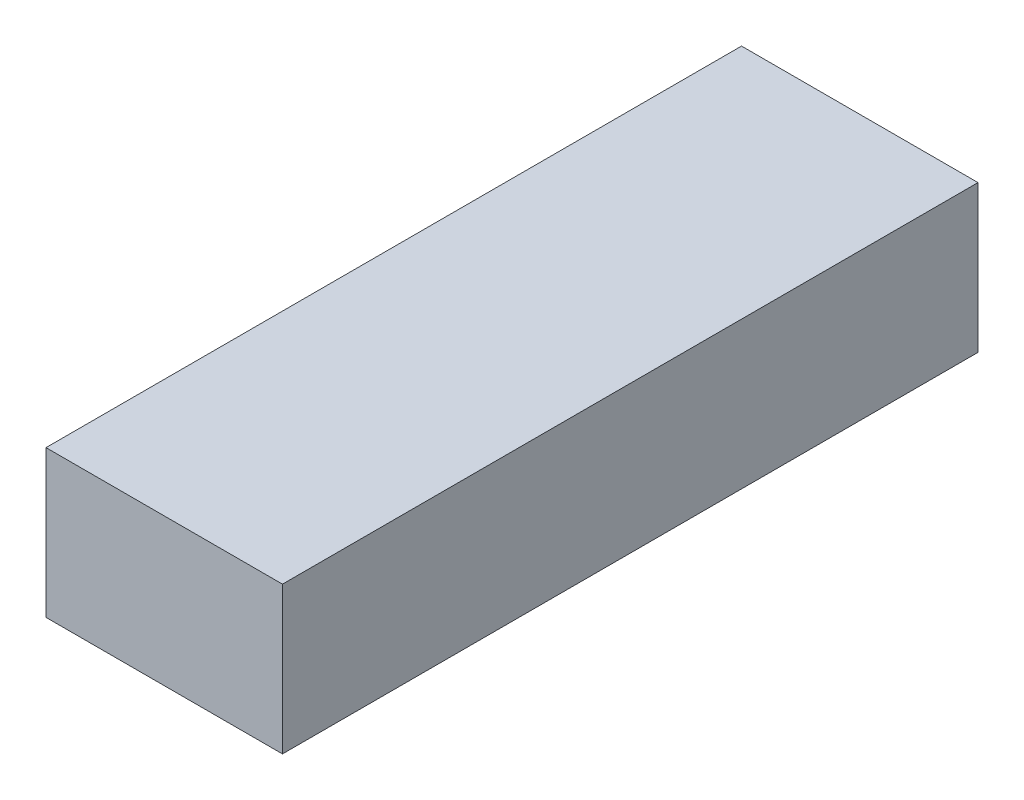
SolidWorks part; units mm, degrees
ref_plane "Front Plane" through (0, 0, 0) normal (0, 0, 1) x (1, 0, 0)
ref_plane "Top Plane" through (0, 0, 0) normal (0, 1, 0) x (1, 0, 0)
ref_plane "Right Plane" through (0, 0, 0) normal (1, 0, 0) x (0, 0, -1)
sketch "Sketch1" plane through (0, 0, 0) normal (0, 1, 0) x (1, 0, 0)
  line L0 (0, 17.3235) -> (0, -20.7882) construction
  line L1 (-3.95, 3.95) -> (3.95, 3.95)
  line L2 (-3.95, 3.95) -> (-3.95, -3.95)
  line L3 (-3.95, -3.95) -> (3.95, -3.95)
  line L4 (3.95, 3.95) -> (3.95, -3.95)
  line L5 (-3.95, 3.95) -> (3.95, -3.95) construction
  line L6 (-3.95, -3.95) -> (3.95, 3.95) construction
  line L7 (3.95, -3.95) -> (5.95, -3.95) construction
  line L8 (-5.95, 26.65) -> (5.95, 26.65)
  line L9 (-5.95, 26.65) -> (-5.95, -8.35)
  line L10 (-5.95, -8.35) -> (5.95, -8.35)
  line L11 (5.95, 26.65) -> (5.95, -8.35)
  line L12 (-5.95, 26.65) -> (5.95, -8.35) construction
  line L13 (-5.95, -8.35) -> (5.95, 26.65) construction
  point P0 (0, 0)
  point P7 (0, 9.15)
  dimension "D1" = 7.9
  dimension "D2" = 2
  dimension "D3" = 4.4
  dimension "D4" = 35
extrude "Boss-Extrude1" add sketch "Sketch1" along normal blind 2.8
sketch "Sketch2" plane through (0, 2.8, 0) normal (0, 1, 0) x (1, 0, 0)
  line L0 (-3.95, 3.95) -> (-3.95, -3.95) construction
  line L1 (-3.45, -3.45) -> (3.45, -3.45)
  line L2 (-3.45, -3.45) -> (-3.45, 3.45)
  line L3 (-3.45, 3.45) -> (3.45, 3.45)
  line L4 (5.95, -8.35) -> (5.95, 26.65)
  line L5 (5.95, 26.65) -> (-5.95, 26.65)
  line L6 (-5.95, 26.65) -> (-5.95, -8.35)
  line L7 (-5.95, -8.35) -> (5.95, -8.35)
  line L8 (5.95, -8.35) -> (5.95, 26.65)
  line L9 (5.95, 26.65) -> (-5.95, 26.65)
  line L10 (-5.95, 26.65) -> (-5.95, -8.35)
  line L11 (-5.95, -8.35) -> (5.95, -8.35)
  line L12 (3.45, -3.45) -> (3.45, 3.45)
  line L13 (-3.45, -3.45) -> (3.45, 3.45) construction
  line L14 (-3.45, 3.45) -> (3.45, -3.45) construction
  line L15 (-3.45, 3.45) -> (-3.95, 3.45) construction
  line L16 (-3.45, 3.45) -> (-3.45, 3.95) construction
  line L17 (3.95, 3.95) -> (-3.95, 3.95) construction
  line L18 (0, 26.65) -> (0, -8.35) construction
  line L20 (3.45, 24.65) -> (-3.45, 24.65)
  line L21 (3.45, 24.65) -> (3.45, 3.45)
  line L22 (3.45, 3.45) -> (-3.45, 3.45)
  line L23 (-3.45, 24.65) -> (-3.45, 3.45)
  line L24 (3.45, 24.65) -> (-3.45, 3.45) construction
  line L25 (3.45, 3.45) -> (-3.45, 24.65) construction
  point P2 (0, 0)
  point P18 (0, 14.05)
  line M12 (5.95, -8.35) -> (5.95, 26.65)
  line M13 (5.95, 26.65) -> (-5.95, 26.65)
  line M14 (-5.95, 26.65) -> (-5.95, -8.35)
  line M15 (-5.95, -8.35) -> (5.95, -8.35)
  line M16 (-3.95, 3.95) -> (3.95, 3.95)
  line M17 (3.95, 3.95) -> (3.95, -3.95)
  line M18 (3.95, -3.95) -> (-3.95, -3.95)
  line M19 (-3.95, -3.95) -> (-3.95, 3.95)
  dimension "D2" = 0.5
  dimension "D3" = 2
  dimension "D1" = 0
extrude "Boss-Extrude2" add sketch "Sketch2" along normal blind 3 contours L23 L20 L21 M15 M12 M13 M14 M16 M17 M18 M19 | L23 L21 L12 L1 L2 M16 M19 M18 M17 region at (0, 2.8, 3.5617) region at (0, 2.8, 7.9803)
sketch "Sketch3" plane through (0, 5.8, 0) normal (0, 1, 0) x (1, 0, 0)
  line L4 (-5.95, -8.35) -> (5.95, -8.35)
  line L5 (5.95, -8.35) -> (5.95, 26.65)
  line L6 (5.95, 26.65) -> (-5.95, 26.65)
  line L7 (-5.95, 26.65) -> (-5.95, -8.35)
  line L8 (-5.95, -8.35) -> (5.95, -8.35)
  line L9 (5.95, -8.35) -> (5.95, 26.65)
  line L10 (5.95, 26.65) -> (-5.95, 26.65)
  line L11 (-5.95, 26.65) -> (-5.95, -8.35)
  dimension "D1" = 0
extrude "Boss-Extrude3" add sketch "Sketch3" along normal blind 1.6
ref_plane "Plane1" through (0, -8.5651, -3.1175) normal (0, -0.9397, -0.342) x (-1, 0, 0)
sketch "Sketch4" plane through (0, -8.5651, -3.1175) normal (0, -0.9397, -0.342) x (-1, 0, 0)
  line L0 (0, 25.0428) -> (0, -7.8464) construction
  line L1 (-5.95, 25.0428) -> (5.95, 25.0428) construction
  line L2 (5.95, -7.8464) -> (-5.95, -7.8464) construction
  line L3 (-5.95, 23.0428) -> (5.95, 23.0428) construction
  line L4 (-5.95, -7.8464) -> (-5.95, 25.0428) construction
  line L5 (5.95, 25.0428) -> (5.95, -7.8464) construction
  line L6 (-4.125, 18.9178) -> (4.125, 18.9178) construction
  circle A0 centre (0, 18.9178) radius 4.125
  circle A1 centre (-4.125, 18.9178) radius 0.3
  circle A2 centre (4.125, 18.9178) radius 0.3
  circle A3 centre (0, 14.7928) radius 0.3
  circle A4 centre (0, 23.0428) radius 0.3
  dimension "D1" = 8.25
  dimension "D3" = 0.6
  dimension "D2" = 2
extrude "Cut-Extrude1" cut sketch "Sketch4" against normal blind 6.8 contours A4 A0 A1 A3 A2 region at (0, -2.0949, -20.8944)
equation "\"LedSize\"= 7.6"
equation "\"D1@Sketch1\"=\"LedSize\"+0.3"
